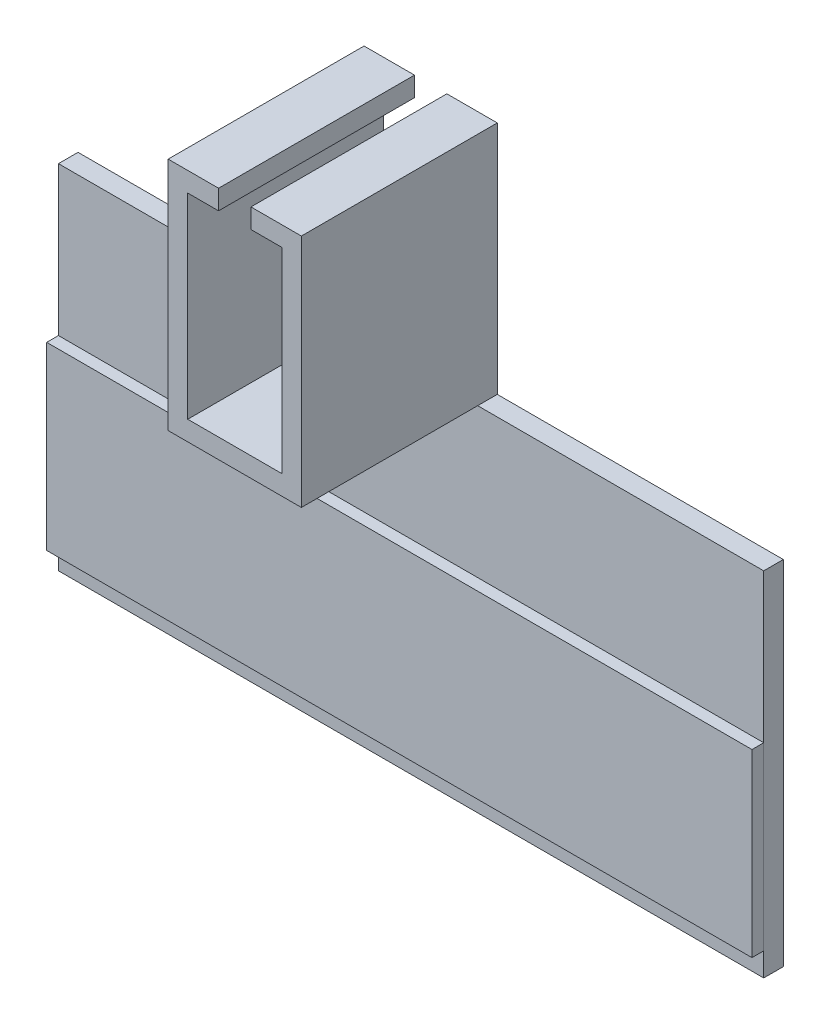
SolidWorks part; units mm, degrees
ref_plane "Ebene vorne" through (0, 0, 0) normal (0, 0, 1) x (1, 0, 0)
ref_plane "Ebene oben" through (0, 0, 0) normal (0, 1, 0) x (1, 0, 0)
ref_plane "Ebene rechts" through (0, 0, 0) normal (1, 0, 0) x (0, 0, -1)
sketch "Skizze1" plane through (0, 0, 0) normal (0, 0, 1) x (1, 0, 0)
  line L0 (-120, 0) -> (120, 0)
  line L1 (120, 0) -> (120, 500)
  line L2 (120, 500) -> (41.3483, 500)
  line L3 (41.3483, 500) -> (41.3483, 550)
  line L4 (41.3483, 550) -> (170, 550)
  line L5 (170, 550) -> (170, -50)
  line L6 (900, -50) -> (900, -950)
  line L7 (900, -950) -> (513.4831, -950)
  line L8 (170, -50) -> (900, -50)
  line L9 (0, -322.4719) -> (0, 738.2022) construction
  line L10 (513.4831, -950) -> (-513.4831, -950)
  line L11 (-170, -50) -> (-900, -50)
  line L12 (-900, -950) -> (-513.4831, -950)
  line L13 (-900, -50) -> (-900, -950)
  line L14 (-170, 550) -> (-170, -50)
  line L15 (-41.3483, 550) -> (-170, 550)
  line L16 (-41.3483, 500) -> (-41.3483, 550)
  line L17 (-120, 500) -> (-41.3483, 500)
  line L18 (-120, 0) -> (-120, 500)
  point P15 (0, -950)
  point P23 (0, 0)
  dimension "D1" = 500
  dimension "D2" = 120
  dimension "D3" = 50
  dimension "D4" = 50
  dimension "D5" = 50
  dimension "D6" = 900
  dimension "D7" = 900
extrude "Aufsatz-Linear austragen1" add sketch "Skizze1" along normal blind 500
sketch "Skizze2" plane through (900, 0, 0) normal (1, 0, 0) x (0, 0, -1)
  line L0 (-500, -50) -> (0, -50) construction
  line L1 (-500, -50) -> (-50, -50)
  line L2 (-500, -50) -> (-500, -950)
  line L3 (-500, -950) -> (-50, -950)
  line L4 (-50, -50) -> (-50, -950)
  line L5 (-500, -950) -> (-500, -50) construction
  line L6 (-500, -950) -> (0, -950) construction
  dimension "D1" = 450
extrude "Schnitt-Linear austragen1" cut sketch "Skizze2" against normal through all
sketch "Skizze3" plane through (900, 0, 0) normal (1, 0, 0) x (0, 0, -1)
  line L0 (-50, -950) -> (-50, -50) construction
  line L1 (-50, -430) -> (-80, -430)
  line L2 (-50, -430) -> (-50, -890)
  line L3 (-50, -890) -> (-80, -890)
  line L4 (-80, -430) -> (-80, -890)
  line L5 (-50, -950) -> (0, -950) construction
  dimension "D1" = 30
  dimension "D2" = 460
  dimension "D3" = 60
extrude "Aufsatz-Linear austragen2" add sketch "Skizze3" against normal blind 1800 separate body
